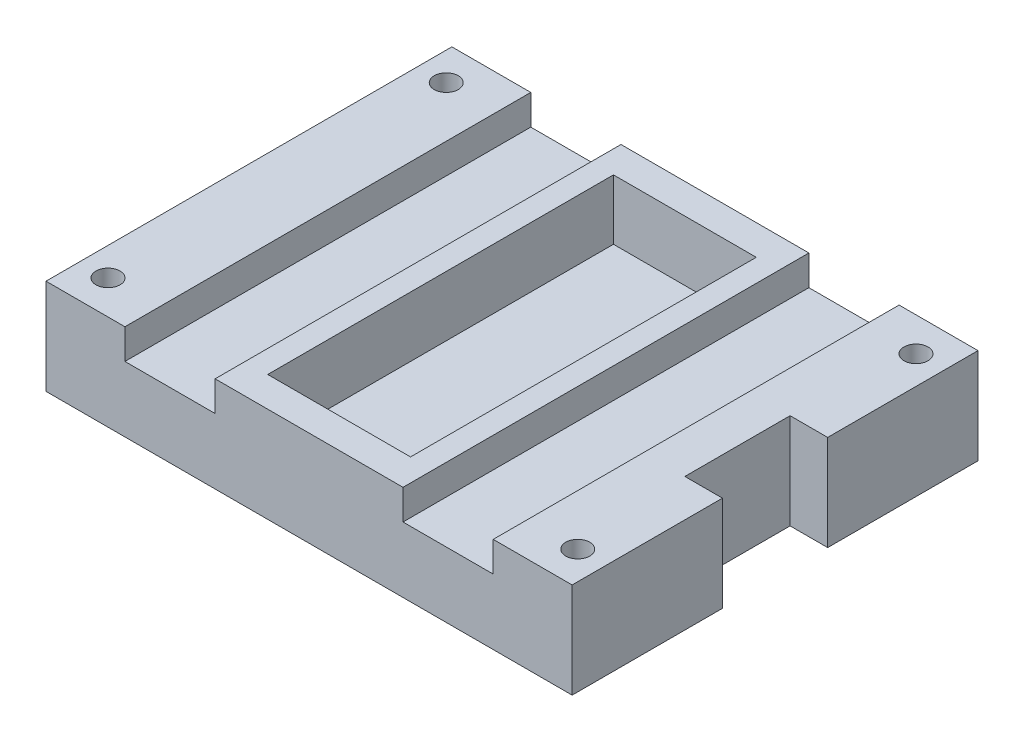
SolidWorks part; units mm, degrees
material "AISI 1020"
ref_plane "Plano frontal" through (0, 0, 0) normal (0, 0, 1) x (1, 0, 0)
ref_plane "Plano superior" through (0, 0, 0) normal (0, 1, 0) x (1, 0, 0)
ref_plane "Plano direito" through (0, 0, 0) normal (1, 0, 0) x (0, 0, -1)
sketch "Esboço1" plane through (0, 0, 0) normal (0, 0, 1) x (1, 0, 0)
  line L1 (0, 0) -> (94, 0)
  line L5 (75.8625, 12.7) -> (0, 12.7)
  line L6 (0, 12.7) -> (0, 0)
  line L8 (75.8625, 12.7) -> (94, 0)
  dimension "D1" = 35
  dimension "D2" = 94
  dimension "D3" = 12.7
extrude "Ressalto-extrusão1" add sketch "Esboço1" along normal blind 98
sketch "Esboço4" plane through (0, 12.7, 0) normal (0, 1, 0) x (1, 0, 0)
  line L0 (75.8625, -98) -> (0, -98) construction
  line L5 (75.8625, 0) -> (0, 0) construction
  line L7 (33, -76) -> (33, -98)
  line L8 (33, -98) -> (0, -98)
  line L9 (0, -76) -> (0, -98)
  line L15 (33, 0) -> (0, 0)
  line L16 (33, 0) -> (33, -22)
  line L18 (0, 0) -> (0, -22)
  line L28 (0, -98) -> (0, 0) construction
  line L29 (70, -98) -> (37, -98)
  line L30 (70, -98) -> (70, -76)
  line L32 (37, -98) -> (37, -76)
  line L33 (70, 0) -> (37, 0)
  line L34 (70, 0) -> (70, -22)
  line L36 (37, 0) -> (37, -22)
  line L56 (70, -22) -> (37, -22)
  line L57 (33, -22) -> (0, -22)
  line L58 (0, -76) -> (33, -76)
  line L59 (37, -76) -> (70, -76)
  dimension "D1" = 22
  dimension "D3" = 33
  dimension "D4" = 22
  dimension "D5" = 33
  dimension "D6" = 22
  dimension "D7" = 22
  dimension "D8" = 4
  dimension "D9" = 33
  dimension "D10" = 4
  dimension "D11" = 33
  dimension "D12" = 22
  dimension "D19" = 22
  dimension "D21" = 22
  dimension "D23" = 22
extrude "Corte-extrusão3" cut sketch "Esboço4" against normal blind 25
sketch "Esboço2" plane through (0, 12.7, 0) normal (0, 1, 0) x (1, 0, 0)
  line L0 (76, -6) -> (76, -92) construction
  line L4 (76, -49) -> (0, -49) construction
  line L5 (75.8625, 0) -> (70, 0) construction
  line L6 (75.8625, -98) -> (70, -98) construction
  line L7 (0, -76) -> (0, -22) construction
  line L8 (0, -76) -> (0, -22) construction
  line L9 (70, -98) -> (70, -76) construction
  circle A0 centre (76, -92) radius 4
  circle A1 centre (76, -6) radius 4
  circle A2 centre (5, -49) radius 4
  dimension "D3" = 8
  dimension "D4" = 8
  dimension "D6" = 8
  dimension "D1" = 6
  dimension "D5" = 6
  dimension "D7" = 5
  dimension "D8" = 6
sketch "Esboço10" plane through (0, 0, 76) normal (0, 0, 1) x (1, 0, 0)
  line L0 (16.5, 12.7) -> (16.5, 0) construction
  line L1 (33, 12.7) -> (0, 12.7) construction
  line L2 (33, 0) -> (0, 0) construction
  line L3 (53.5, 12.7) -> (53.5, 0) construction
  line L4 (37, 12.7) -> (33, 12.7) construction
  line L5 (35, 12.7) -> (35, 0) construction
  line L6 (33, 0) -> (37, 0) construction
  line L7 (10.5, 12.7) -> (22.5, 12.7)
  line L8 (10.5, 12.7) -> (10.5, 8.7)
  line L9 (10.5, 8.7) -> (22.5, 8.7)
  line L10 (22.5, 12.7) -> (22.5, 8.7)
  line L11 (47.5, 12.7) -> (47.5, 8.7)
  line L12 (59.5, 8.7) -> (47.5, 8.7)
  line L13 (59.5, 12.7) -> (59.5, 8.7)
  line L14 (59.5, 12.7) -> (47.5, 12.7)
  dimension "D1" = 4
  dimension "D2" = 6
  dimension "D3" = 6
extrude "Corte-extrusão8" cut sketch "Esboço10" against normal through all
sketch "Esboço11" plane through (0, 12.7, 0) normal (0, 1, 0) x (1, 0, 0)
  line L0 (0, -26.5) -> (29.25, -26.5) construction
  line L1 (0, -76) -> (0, -22) construction
  line L3 (29.25, -71.5) -> (0, -71.5) construction
  line L4 (0, -22) -> (10.5, -22) construction
  line L5 (10.5, -76) -> (0, -76) construction
  line L6 (40.75, -26.5) -> (66.25, -26.5) construction
  line L7 (66.25, -26.5) -> (66.25, -71.5) construction
  line L8 (66.25, -71.5) -> (40.75, -71.5) construction
  circle A2 centre (3.75, -71.5) radius 1.6
  circle A3 centre (3.75, -26.5) radius 1.6
  circle A5 centre (66.25, -26.5) radius 1.6
  circle A6 centre (66.25, -71.5) radius 1.6
  dimension "D6" = 3.2
  dimension "D9" = 3.2
  dimension "D14" = 3.2
  dimension "D15" = 3.2
  dimension "D1" = 4.5
  dimension "D2" = 4.5
  dimension "D3" = 3.75
  dimension "D4" = 3.75
  dimension "D5" = 25.5
  dimension "D11" = 25.5
  dimension "D17" = 45
extrude "Corte-extrusão9" cut sketch "Esboço11" against normal blind 20
sketch "Esboço15" plane through (0, 12.7, 0) normal (0, 1, 0) x (1, 0, 0)
  line L0 (33, -98) -> (33, -76) construction
  line L1 (37, 0) -> (33, 0)
  line L2 (37, 0) -> (37, -22)
  line L3 (37, -22) -> (33, -22)
  line L4 (33, 0) -> (33, -22)
  line L5 (37, -98) -> (33, -98)
  line L6 (37, -98) -> (37, -76)
  line L7 (37, -76) -> (33, -76)
  line L8 (33, -98) -> (33, -76)
extrude "Corte-extrusão11" cut sketch "Esboço15" against normal through all
sketch "Esboço16" plane through (0, 12.7, 0) normal (0, 1, 0) x (1, 0, 0)
  line L0 (70, -98) -> (70, -76) construction
  line L1 (95.8329, 2.473) -> (70, 2.473)
  line L2 (95.8329, 2.473) -> (95.8329, -109.8551)
  line L3 (95.8329, -109.8551) -> (70, -109.8551)
  line L4 (70, 2.473) -> (70, -109.8551)
  line L6 (70, -56) -> (65, -56)
  line L7 (70, -56) -> (70, -42)
  line L8 (70, -42) -> (65, -42)
  line L9 (65, -56) -> (65, -42)
  line L11 (59.5, -22) -> (70, -22) construction
  line M11 (70, -98) -> (75.8625, -98)
  line M12 (75.8625, -98) -> (75.8625, 0)
  line M14 (75.8625, -98) -> (75.8625, 0)
  line M16 (75.8625, -98) -> (75.8625, 0)
  line M17 (75.8625, 0) -> (70, 0)
  dimension "D1" = 14
  dimension "D2" = 20
  dimension "D3" = 5
extrude "Corte-extrusão12" cut sketch "Esboço16" against normal blind 41 and the other way blind 10 contours L1 L4 L3 L2 M17 M16 M14 M12 M11 | L9 L6 L4 L8 region at (85.3815, 12.7, 54.8491) region at (67.5, 12.7, 49)
sketch "Esboço17" plane through (0, 12.7, 0) normal (0, 1, 0) x (1, 0, 0)
  line L1 (70, 0) -> (81.4359, 0)
  line L2 (70, 0) -> (70, -99.5733)
  line L3 (70, -99.5733) -> (81.4359, -99.5733)
  line L4 (81.4359, 0) -> (81.4359, -99.5733)
extrude "Corte-extrusão13" cut sketch "Esboço17" against normal blind 20
sketch "Esboço18" plane through (0, 12.7, 0) normal (0, 1, 0) x (1, 0, 0)
  line L0 (26.5, -69) -> (26.5, -29) construction
  line L1 (25.5, -26) -> (44.5, -26)
  line L2 (25.5, -26) -> (25.5, -72)
  line L3 (25.5, -72) -> (44.5, -72)
  line L4 (44.5, -26) -> (44.5, -72)
  line L5 (41.5, -71) -> (28.5, -71) construction
  dimension "D1" = 46
  dimension "D2" = 19
  dimension "D3" = 1
  dimension "D4" = 1
extrude "Corte-extrusão14" cut sketch "Esboço18" against normal blind 8
